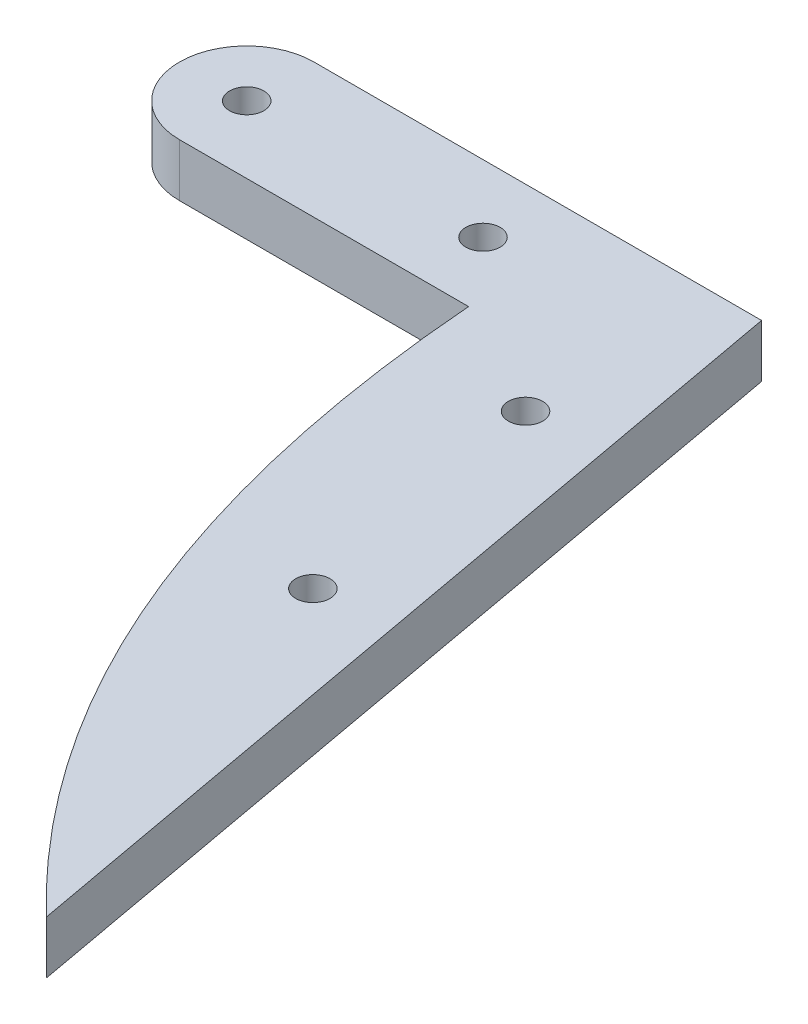
SolidWorks part; units mm, degrees
ref_plane "Front Plane" through (0, 0, 0) normal (0, 0, 1) x (1, 0, 0)
ref_plane "Top Plane" through (0, 0, 0) normal (0, 1, 0) x (1, 0, 0)
ref_plane "Right Plane" through (0, 0, 0) normal (1, 0, 0) x (0, 0, -1)
other "Center of Mass"
sketch "Sketch1" plane through (0, 0, 0) normal (0, 1, 0) x (1, 0, 0)
  line L1 (-11.18, -6.3642) -> (11.18, -6.3642)
  line L2 (-11.18, -6.3642) -> (-11.18, 6.3642)
  line L3 (-11.18, 6.3642) -> (11.18, 6.3642)
  line L4 (11.18, -6.3642) -> (11.18, 6.3642)
  line L5 (-11.18, -6.3642) -> (11.18, 6.3642) construction
  line L6 (-11.18, 6.3642) -> (11.18, -6.3642) construction
  circle A0 centre (-11.18, 0) radius 6.3642
  circle A1 centre (11.18, 0) radius 6.3642
  circle A2 centre (-11.18, 0) radius 1.625
  circle A3 centre (11.18, 0) radius 1.625
  point P0 (0, 0)
  dimension "D2" = 3.25
  dimension "D1" = 22.36
extrude "Boss-Extrude1" add sketch "Sketch1" along normal blind 5 contours A1 L3 A0 L1 | A2 L2 A0 | A2 L2 A0 | A3 L4 A1 | A3 L4 A1 region at (0, 0, 0) region at (-14.0213, 0, 0) region at (-8.3387, 0, 0) region at (8.3387, 0, 0) region at (14.0213, 0, 0)
sketch "Sketch2" plane through (0, 5, 0) normal (0, 1, 0) x (1, 0, 0)
  line L0 (-11.18, 6.3642) -> (11.18, 6.3642) construction
  line L1 (11.18, -6.3642) -> (31.18, -6.3642)
  line L2 (11.18, -6.3642) -> (11.18, 6.3642)
  line L3 (11.18, 6.3642) -> (31.18, 6.3642)
  line L4 (31.18, -6.3642) -> (31.18, 6.3642)
  line L5 (11.18, -6.3642) -> (31.18, 6.3642) construction
  line L6 (11.18, 6.3642) -> (31.18, -6.3642) construction
  line L7 (31.18, 6.3642) -> (46.2292, -76.3642)
  line L8 (16.18, -6.3642) -> (31.18, -6.3642)
  line L9 (16.18, -6.3642) -> (16.18, -76.3642)
  line L10 (16.18, -76.3642) -> (31.18, -76.3642)
  line L11 (31.18, -6.3642) -> (31.18, -76.3642)
  line L12 (16.18, -6.3642) -> (31.18, -76.3642) construction
  line L13 (16.18, -76.3642) -> (31.18, -6.3642) construction
  line L14 (46.2292, -76.3642) -> (31.18, -76.3642)
  circle A0 centre (11.18, 0) radius 1.625 construction
  spline S0 degree 2 poles (16.18, -6.3642) (20.8061, -66.6334) (68.4708, -92.4835) knots 0 0 0 1 1 1
  point P0 (21.18, 0)
  point P5 (11.18, 0)
  point P10 (23.68, -41.3642)
  arc M9 (11.18, -6.3642) -> (11.18, 6.3642) centre (11.18, 0) ccw
  dimension "D1" = 20
  dimension "D2" = 15
  dimension "D3" = 70
  dimension "D4" = 10.31
extrude "Boss-Extrude2" add sketch "Sketch2" against normal blind 5 contours L11 S0 L7 L4 | L1 S0 L11 | L1 L4 L3 M9 region at (23.612, 5, 0) region at (25.3905, 5, 25.4524) region at (36.2562, 5, 43.1154)
sketch "Sketch3" plane through (0, 5, 0) normal (0, 1, 0) x (1, 0, 0)
  line L0 (28.5375, -18.2213) -> (36.7883, -63.5774) construction
  line L1 (36.7883, -63.5774) -> (34.06, -48.5797) construction
  line L2 (31.18, 6.3642) -> (46.2292, -76.3642) construction
  circle A0 centre (27.4506, -12.2462) radius 1.625
  circle A1 centre (31.9249, -36.8426) radius 1.625
  dimension "D1" = 3.25
  dimension "D2" = 25
  dimension "D3" = 7
extrude "Cut-Extrude1" cut sketch "Sketch3" against normal blind 30
sketch "Sketch5" plane through (0, 5, 0) normal (0, 1, 0) x (1, 0, 0)
  circle A0 centre (31.9249, -36.8426) radius 1.625 construction
  circle A1 centre (27.4506, -12.2462) radius 1.625 construction
  circle A2 centre (11.18, 0) radius 1.625 construction
  circle A3 centre (-11.18, 0) radius 1.625 construction
  circle A4 centre (31.9249, -36.8426) radius 1.625
  circle A5 centre (27.4506, -12.2462) radius 1.625
  circle A6 centre (11.18, 0) radius 1.625
  circle A7 centre (-11.18, 0) radius 1.625
  circle A8 centre (-11.18, 0) radius 2.625
  circle A9 centre (11.18, 0) radius 2.625
  circle A10 centre (27.4506, -12.2462) radius 2.625
  circle A11 centre (31.9249, -36.8426) radius 2.625
  dimension "D1" = 1
extrude "Cut-Extrude2" [suppressed] cut sketch "Sketch5" along normal blind 0.8 from surface
